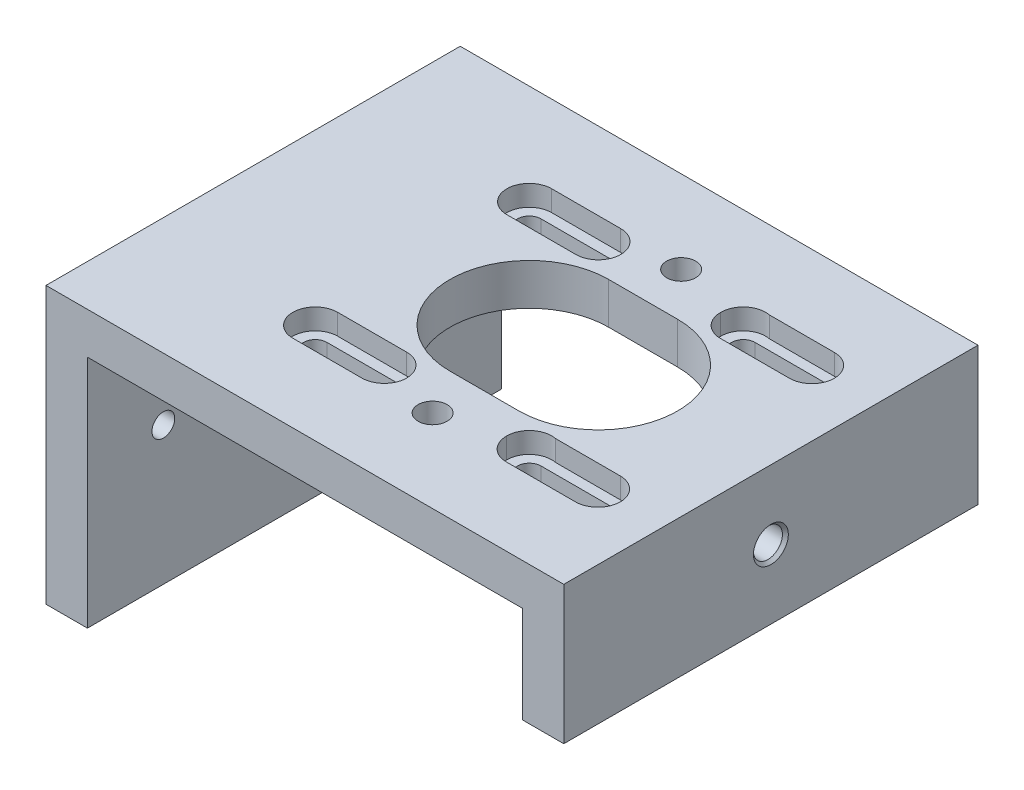
SolidWorks part; units mm, degrees
material "6061 Alloy"
ref_plane "Front Plane" through (0, 0, 0) normal (0, 0, 1) x (1, 0, 0)
ref_plane "Top Plane" through (0, 0, 0) normal (0, 1, 0) x (1, 0, 0)
ref_plane "Right Plane" through (0, 0, 0) normal (1, 0, 0) x (0, 0, -1)
sketch "Sketch1" plane through (0, 0, 0) normal (0, 0, 1) x (1, 0, 0)
  line L0 (0, 0) -> (6, 0)
  line L1 (69, 34) -> (69, 20)
  line L2 (0, 0) -> (0, 40)
  line L3 (0, 40) -> (75, 40)
  line L4 (75, 20) -> (75, 40)
  line L5 (69, 20) -> (75, 20)
  line L6 (6, 0) -> (6, 34)
  line L7 (6, 34) -> (69, 34)
  dimension "D1" = 75
  dimension "D2" = 6
  dimension "D3" = 6
  dimension "D4" = 40
  dimension "D5" = 20
  dimension "D6" = 6
extrude "Boss-Extrude1" add sketch "Sketch1" along normal blind 60
sketch "Sketch2" plane through (0, 40, 0) normal (0, 1, 0) x (1, 0, 0)
  line L0 (24.5, -45.5) -> (55.5, -45.5) construction
  line L1 (24.5, -45.5) -> (24.5, -14.5) construction
  line L2 (40, -18.5) -> (50, -18.5)
  line L3 (0, -60) -> (0, 0) construction
  line L4 (75, -30) -> (0, -30) construction
  line L5 (75, -60) -> (75, 0) construction
  line L6 (50, -41.5) -> (40, -41.5)
  arc A0 (40, -18.5) -> (40, -41.5) centre (40, -30) ccw
  arc A1 (50, -41.5) -> (50, -18.5) centre (50, -30) ccw
  circle A2 centre (40, -30) radius 11.5 construction
  point P2 (24.5, -45.5)
  point P3 (40, -45.5)
  point P4 (24.5, -30)
  point P5 (55.5, -45.5)
  point P6 (24.5, -14.5)
  point P7 (55.5, -14.5)
  dimension "D8" = 23
  dimension "D2" = 31
  dimension "D3" = 31
  dimension "D6" = 10
  dimension "D7" = 40
  dimension "D4" = 2
  dimension "D5" = 2
extrude "Cut-Extrude1" cut sketch "Sketch2" against normal through all
ref_axis "Axis1" through (40, 34, 30) along (0, 1, 0)
hole_wizard "CBORE for M3 Hex Socket Head Cap Screw1" positions "Sketch7" profile "Sketch6" counterbore size "M3" standard "ISO" end condition through all
sketch "Sketch7" plane through (0, 40, 0) normal (0, 1, 0) x (-1, 0, 0)
  line L0 (-24.5, 45.5) -> (-55.5, 45.5) construction
  line L1 (-24.5, 45.5) -> (-24.5, 14.5) construction
  point P0 (-24.5, 45.5)
  point P8 (-55.5, 45.5)
  point P9 (-24.5, 14.5)
  point P10 (-55.5, 14.5)
  point P34 (-40, 45.5)
  point P35 (-24.5, 30)
  dimension "D1" = 31
  dimension "D4" = 31
  dimension "D2" = 2
  dimension "D3" = 2
sketch "Sketch6" plane through (24.5, 40, 45.5) normal (1, 0, 0) x (0, 0, 1)
  line L0 (0, 0) -> (0, 40)
  line L1 (0, 40) -> (1.7, 40)
  line L3 (1.7, 40) -> (1.7, 3)
  line L4 (1.7, 3) -> (3.25, 3)
  line L5 (3.25, 3) -> (3.25, 0)
  line L7 (3.25, 0) -> (0, 0)
  line L11 (0, -6.35) -> (0, 107.95) construction
  dimension "Thru Hole Dia." = 3.4
  dimension "Thru Hole Depth" = 40
  dimension "C'Bore Dia." = 6.5
  dimension "C'Bore Depth" = 3
sketch "Sketch24" plane through (0, 40, 0) normal (0, 1, 0) x (1, 0, 0)
  line L0 (24.5, -14.5) -> (34.5, -14.5) construction
  line L1 (24.5, -12.8) -> (34.5, -12.8)
  line L2 (24.5, -16.2) -> (34.5, -16.2)
  line L3 (65.5138, -30) -> (17.4578, -30) construction
  line L4 (55.5, -14.5) -> (65.5, -14.5) construction
  line L5 (55.5, -12.8) -> (65.5, -12.8)
  line L6 (55.5, -16.2) -> (65.5, -16.2)
  line L7 (24.5, -45.5) -> (34.5, -45.5) construction
  line L8 (24.5, -43.8) -> (34.5, -43.8)
  line L9 (24.5, -47.2) -> (34.5, -47.2)
  line L10 (55.5, -45.5) -> (65.5, -45.5) construction
  line L11 (55.5, -43.8) -> (65.5, -43.8)
  line L12 (55.5, -47.2) -> (65.5, -47.2)
  line L13 (40, -9.8721) -> (40, -50.1279) construction
  arc A0 (24.5, -12.8) -> (24.5, -16.2) centre (24.5, -14.5) ccw
  arc A1 (34.5, -16.2) -> (34.5, -12.8) centre (34.5, -14.5) ccw
  circle A2 centre (24.5, -14.5) radius 1.7 construction
  arc A3 (55.5, -12.8) -> (55.5, -16.2) centre (55.5, -14.5) ccw
  arc A4 (65.5, -16.2) -> (65.5, -12.8) centre (65.5, -14.5) ccw
  arc A5 (24.5, -43.8) -> (24.5, -47.2) centre (24.5, -45.5) ccw
  arc A6 (34.5, -47.2) -> (34.5, -43.8) centre (34.5, -45.5) ccw
  arc A7 (55.5, -43.8) -> (55.5, -47.2) centre (55.5, -45.5) ccw
  arc A8 (65.5, -47.2) -> (65.5, -43.8) centre (65.5, -45.5) ccw
  point P3 (29.5, -14.5)
  point P18 (60.5, -14.5)
  point P25 (29.5, -45.5)
  point P32 (60.5, -45.5)
  dimension "D1" = 10
  dimension "D2" = 2
  dimension "D3" = 2
extrude "Cut-Extrude5" cut sketch "Sketch24" against normal up to next
sketch "Sketch25" plane through (0, 40, 0) normal (0, 1, 0) x (1, 0, 0)
  line L0 (24.5, -14.5) -> (34.5, -14.5) construction
  line L1 (24.5, -11.25) -> (34.5, -11.25)
  line L2 (24.5, -17.75) -> (34.5, -17.75)
  line L3 (55.5, -14.5596) -> (65.5, -14.5596) construction
  line L4 (55.5, -11.3096) -> (65.5, -11.3096)
  line L5 (55.5, -17.8096) -> (65.5, -17.8096)
  line L6 (24.5, -45.5) -> (34.5, -45.5) construction
  line L7 (24.5, -42.25) -> (34.5, -42.25)
  line L8 (24.5, -48.75) -> (34.5, -48.75)
  line L9 (55.5, -45.5596) -> (65.5, -45.5596) construction
  line L10 (55.5, -42.3096) -> (65.5, -42.3096)
  line L11 (55.5, -48.8096) -> (65.5, -48.8096)
  arc A0 (24.5, -11.25) -> (24.5, -17.75) centre (24.5, -14.5) ccw
  arc A1 (34.5, -17.75) -> (34.5, -11.25) centre (34.5, -14.5) ccw
  arc A2 (27.2699, -12.8) -> (27.2699, -16.2) centre (24.5, -14.5) ccw construction
  arc A3 (55.5, -11.3096) -> (55.5, -17.8096) centre (55.5, -14.5596) ccw
  arc A4 (65.5, -17.8096) -> (65.5, -11.3096) centre (65.5, -14.5596) ccw
  arc A5 (24.5, -42.25) -> (24.5, -48.75) centre (24.5, -45.5) ccw
  arc A6 (34.5, -48.75) -> (34.5, -42.25) centre (34.5, -45.5) ccw
  arc A7 (55.5, -42.3096) -> (55.5, -48.8096) centre (55.5, -45.5596) ccw
  arc A8 (65.5, -48.8096) -> (65.5, -42.3096) centre (65.5, -45.5596) ccw
  point P4 (29.5, -14.5)
  point P17 (60.5, -14.5596)
  point P24 (29.5, -45.5)
  point P31 (60.5, -45.5596)
  dimension "D1" = 10
  dimension "D2" = 2
  dimension "D3" = 2
extrude "Cut-Extrude6" cut sketch "Sketch25" against normal blind 3
hole_wizard "M5 Tapped Hole1" positions "Sketch14" profile "Sketch15" tap size "M5" standard "ISO" end condition through all
sketch "Sketch14" plane through (0, 40, 0) normal (0, 1, 0) x (-1, 0, 0)
  line L0 (-44, 12) -> (-44, 48) construction
  point P0 (-44, 12)
  point P1 (-44, 48)
  dimension "D1" = 18
  dimension "D2" = 18
  dimension "D3" = 4
sketch "Sketch15" plane through (44, 40, 12) normal (1, 0, 0) x (0, 0, 1)
  line L0 (0, 0) -> (0, 40)
  line L1 (0, 40) -> (2.1, 40)
  line L2 (2.1, 40) -> (2.1, 0)
  line L5 (2.1, 0) -> (0, 0)
  line L11 (0, -6.35) -> (0, 107.95) construction
  dimension "Thru Tap Drill Dia." = 4.2
  dimension "Thru Tap Drill Depth" = 40
cosmetic thread "Hole Thread5" parameters "D2"=5
cosmetic thread "Hole Thread6" parameters "D2"=5
hole_wizard "M4 Tapped Hole1" positions "Sketch20" profile "Sketch19" tap size "M4" standard "ISO" end condition up to next
sketch "Sketch20" plane through (0, 0, 0) normal (-1, 0, 0) x (0, 0, 1)
  line L0 (30, 40) -> (30, 0) construction
  line L1 (60, 40) -> (0, 40) construction
  line L2 (60, 0) -> (0, 0) construction
  point P0 (11, 20)
  point P16 (49, 20)
  dimension "D1" = 20
  dimension "D3" = 38
cosmetic thread "Hole Thread8" parameters "D2"=4
cosmetic thread "Hole Thread10" parameters "D2"=4
sketch "Sketch19" plane through (0, 20, 11) normal (0, 1, 0) x (0, 0, 1)
  line L0 (0, 0) -> (0, 6)
  line L1 (0, 6) -> (1.65, 6)
  line L2 (1.65, 6) -> (1.65, 0.6)
  line L3 (1.65, 0.6) -> (2.25, 0)
  line L5 (2.25, 0) -> (0, 0)
  line L6 (-1.65, 0.6) -> (-2.25, 0) construction
  line L11 (0, -6.35) -> (0, 107.95) construction
  dimension "Thru Tap Drill Dia." = 3.3
  dimension "Thru Tap Drill Depth" = 6
  dimension "Near C'Sink Dia." = 4.5
  dimension "Near C'Sink Angle" = 90
hole_wizard "M5 Tapped Hole2" positions "Sketch23" profile "Sketch22" tap size "M5" standard "ISO" end condition up to next
sketch "Sketch23" plane through (75, 0, 0) normal (1, 0, 0) x (0, 0, -1)
  line L0 (-30, 34) -> (-30, 40) construction
  line L1 (-60, 40) -> (0, 40) construction
  point P0 (-30, 30)
  dimension "D1" = 10
cosmetic thread "Hole Thread11" parameters "D2"=5
sketch "Sketch22" plane through (75, 30, 30) normal (0, 1, 0) x (0, 0, -1)
  line L0 (0, 0) -> (0, 6)
  line L1 (0, 6) -> (2.1, 6)
  line L2 (2.1, 6) -> (2.1, 0.425)
  line L3 (2.1, 0.425) -> (2.525, 0)
  line L5 (2.525, 0) -> (0, 0)
  line L6 (-2.1, 0.425) -> (-2.525, 0) construction
  line L11 (0, -6.35) -> (0, 107.95) construction
  dimension "Thru Tap Drill Dia." = 4.2
  dimension "Thru Tap Drill Depth" = 6
  dimension "Near C'Sink Dia." = 5.05
  dimension "Near C'Sink Angle" = 90
